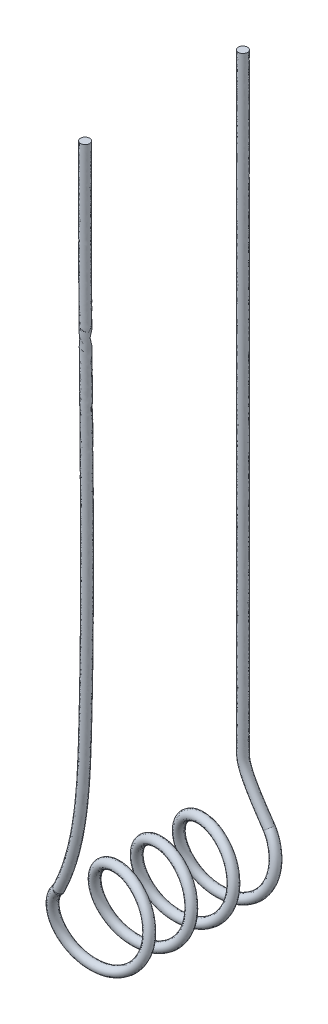
SolidWorks part; units mm, degrees
ref_plane "Front Plane" through (0, 0, 0) normal (0, 0, 1) x (1, 0, 0)
ref_plane "Top Plane" through (0, 0, 0) normal (0, 1, 0) x (1, 0, 0)
ref_plane "Right Plane" through (0, 0, 0) normal (1, 0, 0) x (0, 0, -1)
sketch "Sketch1" plane through (0, 0, 0) normal (0, 0, 1) x (1, 0, 0)
  circle A0 centre (0, 0) radius 0.8255
  dimension "D1" = 1.651
curve "Helix/Spiral1" pitch 0.9333 height 3.4999 radius 0.8255 left hand yes centre (0, 0, 0) axis (0, 0, 1) start towards (0.7071, 0.7071, 0)
ref_plane "Plane4" through (0, 0, 3.5) normal (0, 0, 1) x (1, 0, 0)
sketch "Sketch16" plane through (0, 0, 3.5) normal (0, 0, 1) x (1, 0, 0)
  line L0 (0, 0) -> (0, 7.8175) construction
  spline S0 degree 3 poles (-0.5859, 0.5855) (-0.0868, 1.6137) (0.1497, 6.6139) (-0.0311, 11.4508) (0, 15.24) knots 0 0 0 0 0.230363 1 1 1 1
  point P2 (-0.5859, 0.5855)
  dimension "D1" = 15.24
sketch "Sketch17" plane through (0, 0, 0) normal (0, 0, 1) x (1, 0, 0)
  line L0 (0, 0) -> (0, 4.3257) construction
  spline S0 degree 3 poles (0.5837, 0.5837) (0.0409, 1.3649) (-0.0088, 1.6501) (0.0056, 2.1501) (-0.0034, 13.9216) (0, 15.24) knots 0 0 0 0 0.357027 0.532141 1 1 1 1
  dimension "D1" = 15.24
sweep "Sweep1" add path "Sketch17" circular profile diameter 0.2032 parameters "D3"=0.2032
sweep "Sweep2" add path "Helix/Spiral1" circular profile diameter 0.2032 parameters "D3"=0.2032
sweep "Sweep3" add path "Sketch16" circular profile diameter 0.2032 parameters "D3"=0.2032
